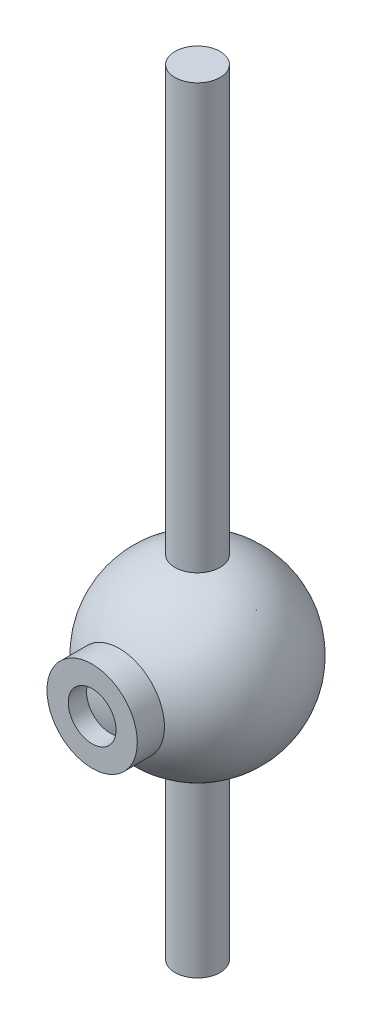
SolidWorks part; units mm, degrees
material "Plain Carbon Steel"
ref_plane "Front Plane" through (0, 0, 0) normal (0, 0, 1) x (1, 0, 0)
ref_plane "Top Plane" through (0, 0, 0) normal (0, 1, 0) x (1, 0, 0)
ref_plane "Right Plane" through (0, 0, 0) normal (1, 0, 0) x (0, 0, -1)
sketch "Sketch1" plane through (0, 0, 0) normal (0, 0, 1) x (1, 0, 0)
  circle A0 centre (0, 0) radius 6
  circle A1 centre (0, 0) radius 3.175
  dimension "D1" = 12
  dimension "D2" = 6.35
extrude "Boss-Extrude1" add sketch "Sketch1" along normal blind 7 from offset 7
sketch "Sketch2" plane through (0, 0, 0) normal (0, 0, 1) x (1, 0, 0)
  line L0 (0, -35) -> (0, 68) construction
  line L1 (0, -35) -> (3, -35)
  line L2 (3, -35) -> (3, -11.619)
  line L3 (3, 11.619) -> (3, 68)
  line L4 (3, 68) -> (0, 68)
  line L5 (0, 68) -> (0, -35)
  arc A0 (3, -11.619) -> (3, 11.619) centre (0, 0) ccw
  dimension "D1" = 12
  dimension "D2" = 35
  dimension "D3" = 68
  dimension "D4" = 3
revolve "Revolve1" add sketch "Sketch2" angle 360 about L0
